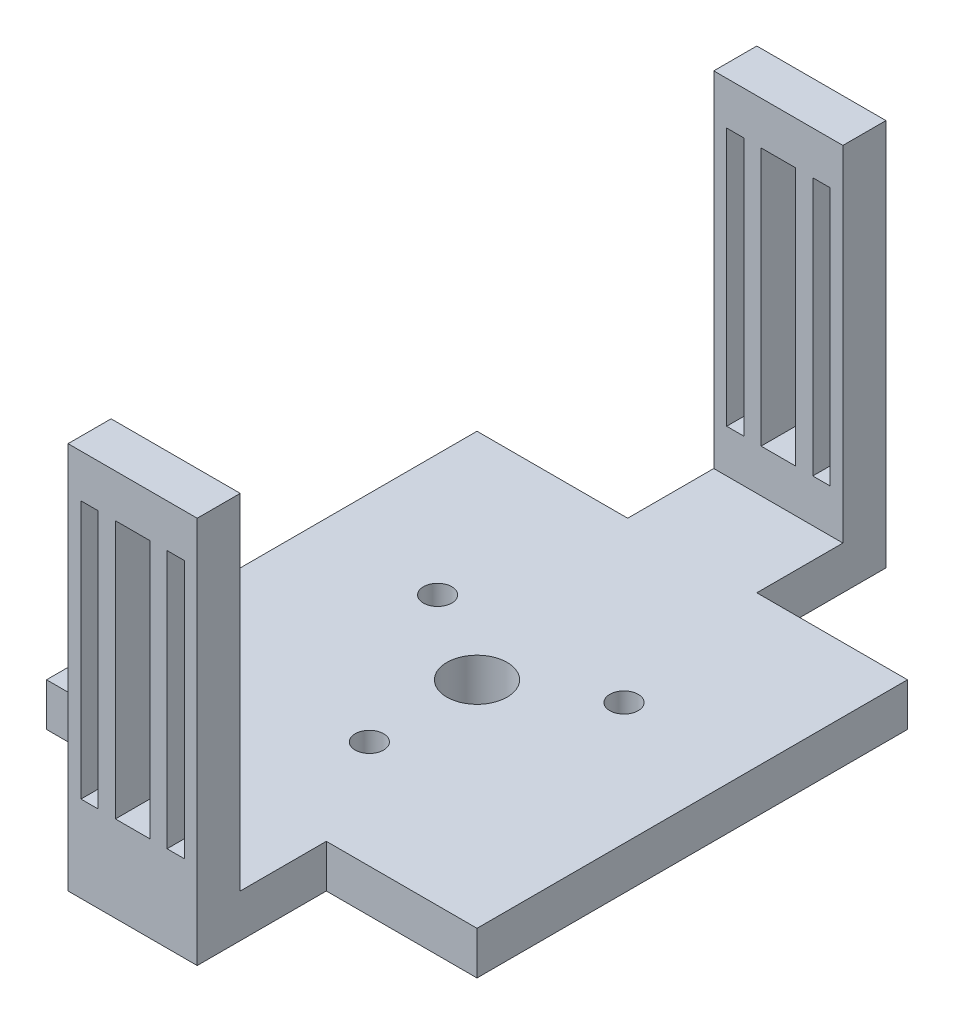
SolidWorks part; units mm, degrees
ref_plane "Plano frontal" through (0, 0, 0) normal (0, 0, 1) x (1, 0, 0)
ref_plane "Plano superior" through (0, 0, 0) normal (0, 1, 0) x (1, 0, 0)
ref_plane "Plano direito" through (0, 0, 0) normal (1, 0, 0) x (0, 0, -1)
sketch "Esboço1" plane through (0, 0, 0) normal (0, 0, 1) x (1, 0, 0)
  line L17 (-15, -40) -> (15, -40)
  line L18 (-15, -40) -> (-15, 40)
  line L19 (-15, 40) -> (15, 40)
  line L20 (15, -40) -> (15, 40)
  line L21 (-4, -30) -> (4, -30)
  line L22 (-4, -30) -> (-4, 30)
  line L23 (-4, 30) -> (4, 30)
  line L24 (4, -30) -> (4, 30)
  line L25 (-4, -30) -> (4, 30) construction
  line L26 (-4, 30) -> (4, -30) construction
  line L27 (-15, -40) -> (15, -40)
  line L28 (-15, -40) -> (-15, -50)
  line L29 (-15, -50) -> (15, -50)
  line L30 (15, -40) -> (15, -50)
  line L32 (-50, -40) -> (50, -40)
  line L33 (-50, -40) -> (-50, -50)
  line L34 (-50, -50) -> (50, -50)
  line L35 (50, -40) -> (50, -50)
  line L39 (-8, 30) -> (-12, 30)
  line L40 (-8, 30) -> (-8, -30)
  line L41 (-8, -30) -> (-12, -30)
  line L42 (-12, 30) -> (-12, -30)
  line L43 (8, 30) -> (12, 30)
  line L44 (8, 30) -> (8, -30)
  line L45 (8, -30) -> (12, -30)
  line L46 (12, 30) -> (12, -30)
  point P0 (0, 0)
extrude "Ressalto-extrusão1" add sketch "Esboço1" along normal blind 10 contours L17 L20 L19 L18 L24 L21 L22 L23 region at (-14.1456, 0, 0)
extrude "Ressalto-extrusão3" add sketch "Esboço1<4>" along normal blind 80 contours L30 L17 L28 L29 region at (0, -45, 0)
sketch "Esboço1<4>" plane through (0, 0, 0) normal (0, 0, 1) x (1, 0, 0) same geometry as "Esboço1"
ref_plane "Plano1" through (0, 0, 80) normal (0, 0, 1) x (1, 0, 0)
extrude "Ressalto-extrusão5" add sketch "Esboço1<6>" against normal blind 50 from surface contours L33 L34 L28 L32 | L35 L32 L30 L34 region at (-32.5, -45, 0) region at (32.5, -45, 0) starting at plane "Plano1"
sketch "Esboço1<6>" plane through (0, 0, 0) normal (0, 0, 1) x (1, 0, 0) same geometry as "Esboço1"
mirror "Espelhar2" about plane through (0, 0, 80) normal (0, 0, 1) of "Ressalto-extrusão5", "Ressalto-extrusão3", "Ressalto-extrusão1"
sketch "Esboço3" plane through (0, -40, 0) normal (0, 1, 0) x (1, 0, 0)
  circle A0 centre (0, -80) radius 7
  circle A1 centre (0, -105) radius 3.3
  circle A2 centre (-21.6506, -67.5) radius 3.3
  circle A3 centre (21.6506, -67.5) radius 3.3
  point P11 (0, -80)
  dimension "D1" = 3
extrude "Corte-extrusão1" cut sketch "Esboço3" against normal up to next
